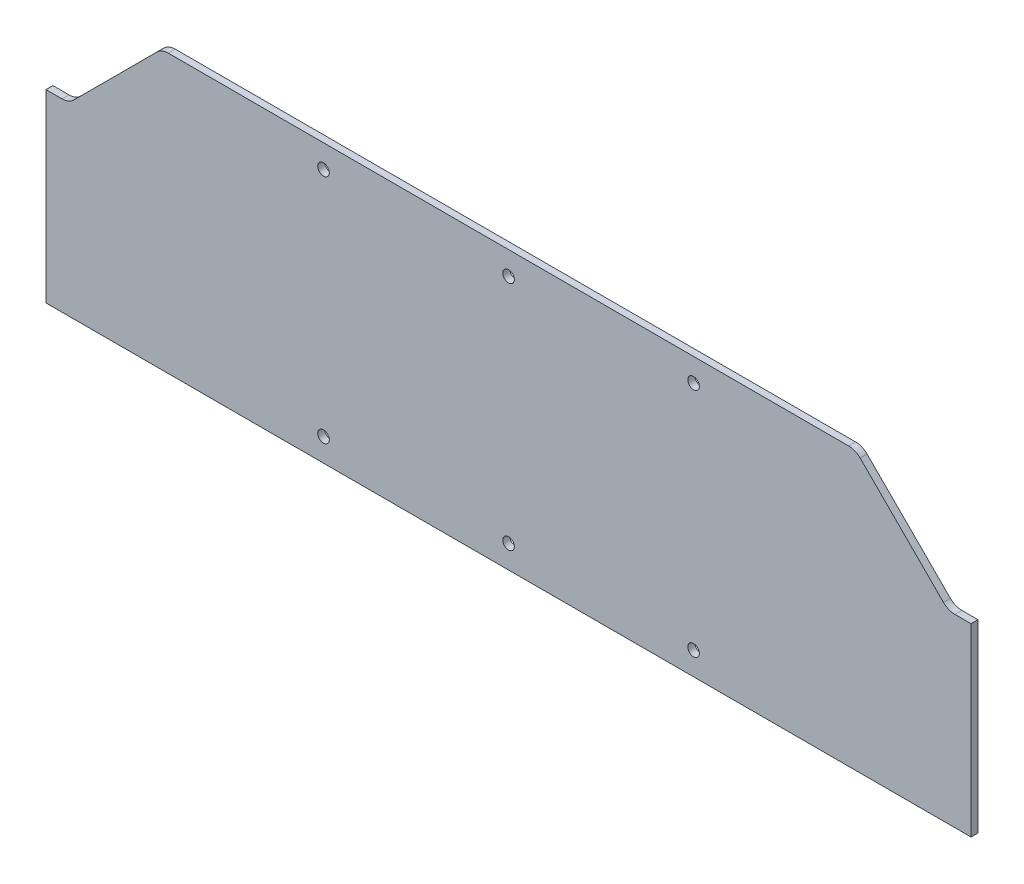
SolidWorks part; units mm, degrees
material "Acrylic (Medium-high impact)"
ref_plane "Front Plane" through (0, 0, 0) normal (0, 0, 1) x (1, 0, 0)
ref_plane "Top Plane" through (0, 0, 0) normal (0, 1, 0) x (1, 0, 0)
ref_plane "Right Plane" through (0, 0, 0) normal (1, 0, 0) x (0, 0, -1)
sketch "Sketch1" plane through (0, 0, 0) normal (0, 0, 1) x (1, 0, 0)
  line L1 (-200, -60) -> (200, -60)
  line L2 (-200, -60) -> (-200, 60)
  line L3 (-200, 60) -> (200, 60)
  line L4 (200, -60) -> (200, 60)
  line L5 (-200, -60) -> (200, 60) construction
  line L6 (-200, 60) -> (200, -60) construction
  point P0 (0, 0)
  dimension "D1" = 400
  dimension "D2" = 120
extrude "Boss-Extrude1" add sketch "Sketch1" along normal blind 3
sketch "Sketch2" plane through (0, 0, 0) normal (0, 0, -1) x (-1, 0, 0)
  line L0 (0, -1000) -> (0, 49000) construction
  line L1 (-200, 60) -> (200, 60) construction
  line L2 (200, 60) -> (147.1005, 60)
  line L3 (200, 60) -> (200, 19.8995)
  line L7 (152.0503, 57.9497) -> (188.0503, 21.9497)
  line L8 (200, 60) -> (200, -60) construction
  line L9 (-152.0503, 57.9497) -> (-188.0503, 21.9497)
  line L10 (-200, 60) -> (-200, 19.8995)
  line L11 (-200, 60) -> (-147.1005, 60)
  line L12 (-193, 19.8995) -> (-200, 19.8995)
  line L13 (-200, -60) -> (-200, 60) construction
  line L14 (193, 19.8995) -> (200, 19.8995)
  line L15 (200, 60) -> (200, -60) construction
  arc A2 (188.0503, 21.9497) -> (193, 19.8995) centre (193, 26.8995) ccw
  arc A3 (152.0503, 57.9497) -> (147.1005, 60) centre (147.1005, 53) ccw
  arc A4 (-152.0503, 57.9497) -> (-147.1005, 60) centre (-147.1005, 53) cw
  arc A5 (-188.0503, 21.9497) -> (-193, 19.8995) centre (-193, 26.8995) cw
  point P3 (0, 0)
  point P30 (0, 0)
  dimension "D3" = 7
  dimension "D7" = 7
  dimension "D1" = 7
  dimension "D2" = 33.1005
  dimension "D4" = 50.9117
  dimension "D5" = 7
  dimension "D6" = 147.1005
  dimension "D8" = 2.0503
extrude "Cut-Extrude1" cut sketch "Sketch2" against normal up to next
sketch "Sketch3" plane through (0, 0, 3) normal (0, 0, 1) x (1, 0, 0)
  line L2 (147.1005, 50) -> (-147.1005, 50)
  line L3 (147.1005, 50) -> (-147.1005, 50) construction
  line L4 (0, -1000) -> (0, 49000) construction
  line L5 (-200, -50) -> (200, -50)
  line L6 (-200, -50) -> (200, -50) construction
  circle A1 centre (-80, 50) radius 2.5
  circle A2 centre (0, 50) radius 2.5
  circle A4 centre (0, -50) radius 2.5
  circle A5 centre (-80, -50) radius 2.5
  circle A6 centre (80, -50) radius 2.5
  circle A7 centre (80, 50) radius 2.5
  point P1 (0, 0)
  point P11 (0, 0)
  dimension "D3" = 5
  dimension "D4" = 80
  dimension "D1" = 10
  dimension "D2" = 10
extrude "Cut-Extrude2" cut sketch "Sketch3" against normal up to next
